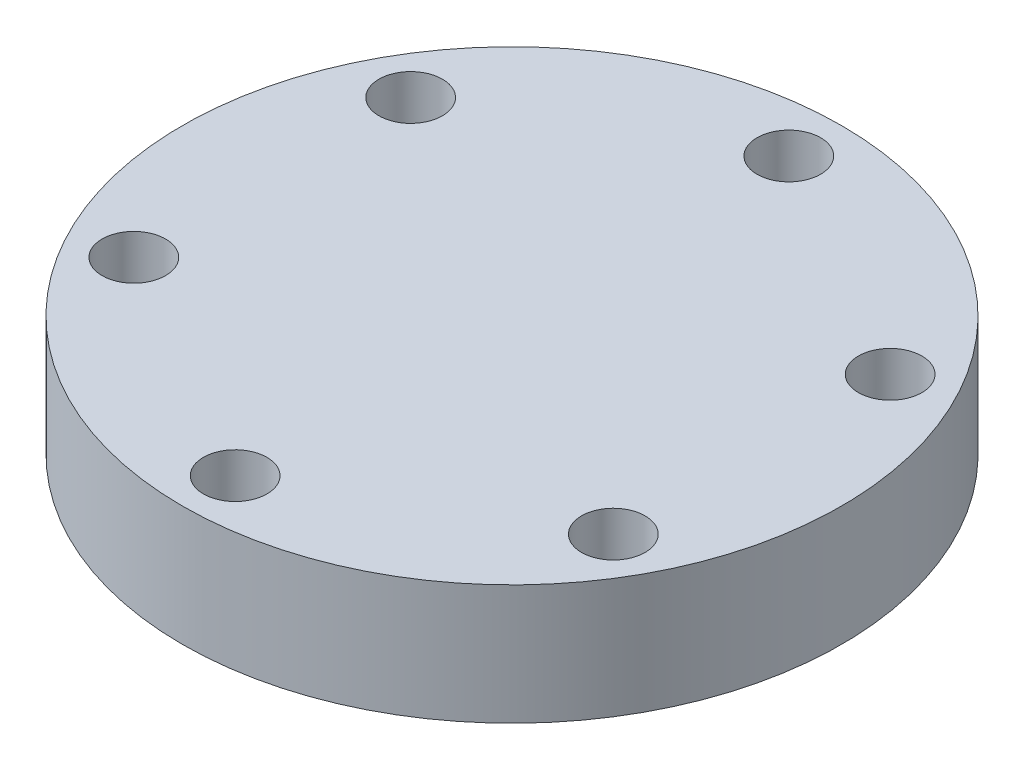
SolidWorks part; units mm, degrees
ref_plane "Front Plane" through (0, 0, 0) normal (0, 0, 1) x (1, 0, 0)
ref_plane "Top Plane" through (0, 0, 0) normal (0, 1, 0) x (1, 0, 0)
ref_plane "Right Plane" through (0, 0, 0) normal (1, 0, 0) x (0, 0, -1)
sketch "Sketch1" plane through (0, 0, 0) normal (0, 1, 0) x (1, 0, 0)
  circle A0 centre (0, 0) radius 34.925
  dimension "D1" = 69.85
extrude "Extrude1" add sketch "Sketch1" along normal blind 12.7
sketch "Sketch2" plane through (0, 0, 0) normal (0, 1, 0) x (1, 0, 0)
  circle A0 centre (0, 0) radius 17.399
  dimension "D1" = 34.798
extrude "Cut-Extrude1" [suppressed] cut sketch "Sketch2" along normal through all
sketch "Sketch3" plane through (0, 0, 0) normal (0, 1, 0) x (1, 0, 0)
  circle A0 centre (0, 29.337) radius 3.3655
  dimension "D1" = 6.731
  dimension "D2" = 29.337
extrude "Cut-Extrude2" cut sketch "Sketch3" along normal blind 12.7
ref_axis "Axis1" through (0, 35.8582, 0) along (0, -1, 0)
pattern_circular "CirPattern1" count 6 over 360 about axis through (0, 35.8582, 0) along (0, -1, 0) of "Cut-Extrude2"
sketch "Sketch4" plane through (0, 0, 0) normal (0, 1, 0) x (1, 0, 0)
  line L0 (0, 0) -> (0, 16.8619)
sketch "Sketch5" plane through (0, 0, 0) normal (0, 1, 0) x (1, 0, 0)
  circle A0 centre (0, 0) radius 3.175
  dimension "D1" = 6.35
extrude "Extrude2" [suppressed] add sketch "Sketch5" against normal blind 101.6 and the other way blind 25.4
